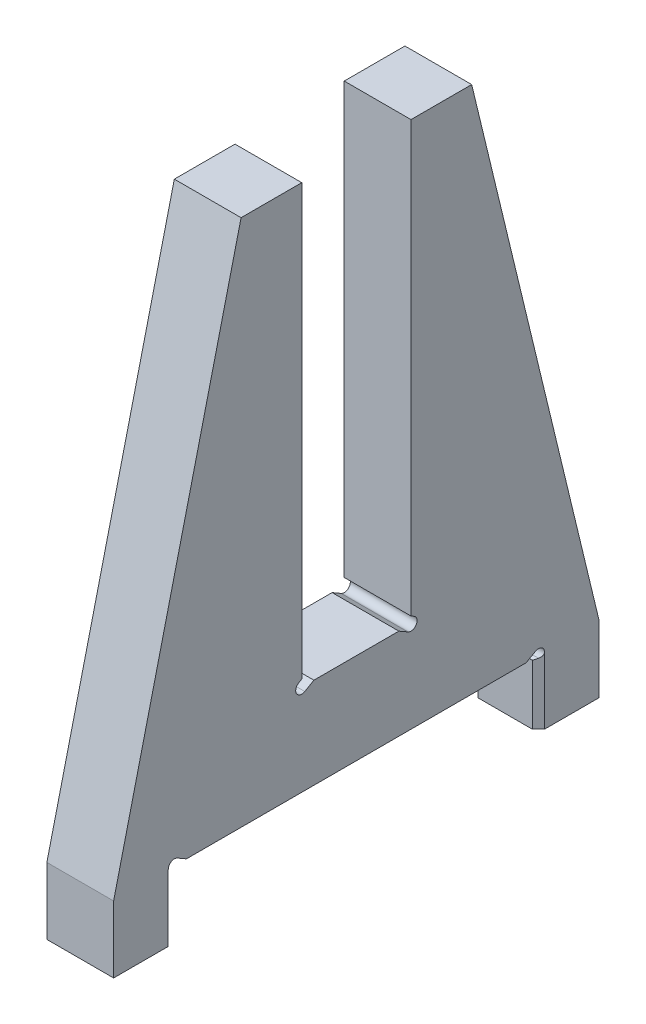
SolidWorks part; units mm, degrees
ref_plane "Piano frontale" through (0, 0, 0) normal (0, 0, 1) x (1, 0, 0)
ref_plane "Piano superiore" through (0, 0, 0) normal (0, 1, 0) x (1, 0, 0)
ref_plane "Piano destro" through (0, 0, 0) normal (1, 0, 0) x (0, 0, -1)
sketch "Sketch1" plane through (0, 0, 0) normal (1, 0, 0) x (0, 0, -1)
  line L0 (0, 53.7437) -> (0, -38.9246) construction
  line L1 (28, 1.3919) -> (-28, 1.3919)
  line L2 (-30, 0.2372) -> (-30, -9.6081)
  line L3 (-28, 1.3919) -> (-29.5, 2.2579)
  line L4 (-30, -9.6081) -> (-40, -9.6081)
  line L5 (-30.5, 0.5259) -> (-30, 0.2372)
  line L6 (-40, -9.6081) -> (-40, 1.3919)
  line L7 (7, 16.3919) -> (-7, 16.3919)
  line L8 (-9, 17.5466) -> (-9, 88.3919)
  line L9 (-7, 16.3919) -> (-8.5, 15.5259)
  line L10 (-9, 88.3919) -> (-19, 88.3919)
  line L11 (-40, 1.3919) -> (-19, 88.3919)
  line L12 (-9.5, 17.2579) -> (-9, 17.5466)
  line L13 (9.5, 17.2579) -> (9, 17.5466)
  line L14 (40, 1.3919) -> (19, 88.3919)
  line L15 (9, 88.3919) -> (19, 88.3919)
  line L16 (7, 16.3919) -> (8.5, 15.5259)
  line L17 (9, 17.5466) -> (9, 88.3919)
  line L18 (40, -9.6081) -> (40, 1.3919)
  line L19 (30.5, 0.5259) -> (30, 0.2372)
  line L20 (30, -9.6081) -> (40, -9.6081)
  line L21 (28, 1.3919) -> (29.5, 2.2579)
  line L22 (30, 0.2372) -> (30, -9.6081)
  arc A0 (-29.5, 2.2579) -> (-30.5, 0.5259) centre (-30, 1.3919) ccw
  arc A2 (-9.5, 17.2579) -> (-8.5, 15.5259) centre (-9, 16.3919) ccw
  arc A3 (9.5, 17.2579) -> (8.5, 15.5259) centre (9, 16.3919) cw
  arc A4 (29.5, 2.2579) -> (30.5, 0.5259) centre (30, 1.3919) cw
  point P32 (0, 16.3919)
  point P36 (0, 0)
  dimension "D3" = 98
  dimension "D10" = 2
  dimension "D7" = 72
  dimension "D1" = 30
  dimension "D2" = 2
  dimension "D4" = 10
  dimension "D5" = 11
  dimension "D6" = 11
  dimension "D8" = 30
  dimension "D9" = 2
  dimension "D11" = 10
  dimension "D12" = 40
extrude "Boss-Extrude1" add sketch "Sketch1" along normal blind 11
chamfer "Chamfer4" distance 1 angle 45 2 edges at (0, -4.6855, 30) (11, -4.6855, 30)
chamfer "Chamfer5" distance 1 angle 45 2 edges at (0, -4.6855, -30) (11, -4.6855, -30)
